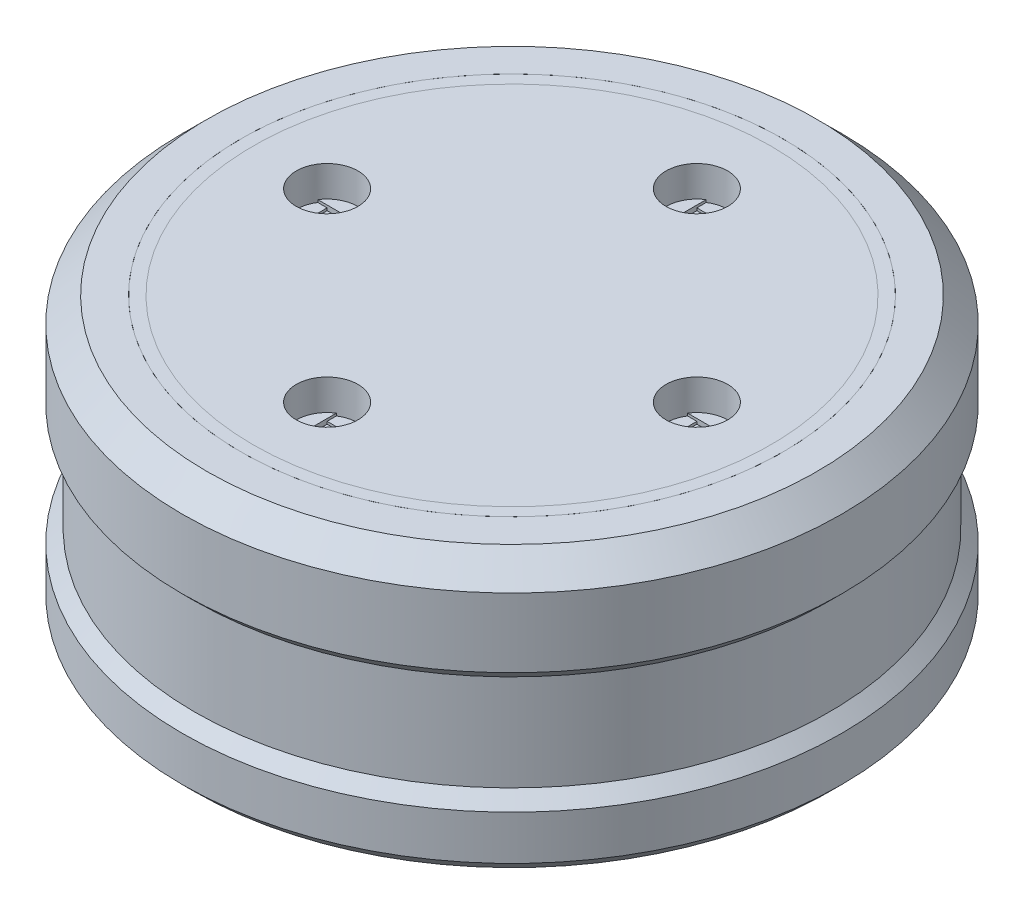
SolidWorks part; units mm, degrees
ref_plane "Front Plane" through (0, 0, 0) normal (0, 0, 1) x (1, 0, 0)
ref_plane "Top Plane" through (0, 0, 0) normal (0, 1, 0) x (1, 0, 0)
ref_plane "Right Plane" through (0, 0, 0) normal (1, 0, 0) x (0, 0, -1)
sketch "Sketch1" plane through (0, 0, 0) normal (0, 1, 0) x (1, 0, 0)
  circle A0 centre (0, 0) radius 15 construction
  circle A1 centre (0, 0) radius 26.75
  circle A2 centre (0, 15) radius 1.35
  circle A3 centre (15, 0) radius 1.35
  circle A4 centre (0, -15) radius 1.35
  circle A5 centre (-15, 0) radius 1.35
  dimension "D1" = 30
  dimension "D2" = 53.5
  dimension "D3" = 2.7
extrude "Boss-Extrude1" add sketch "Sketch1" along normal blind 25
sketch "Sketch2" plane through (0, 0, 0) normal (0, -1, 0) x (1, 0, 0)
  circle A0 centre (0, 0) radius 25
  dimension "D1" = 50
extrude "Cut-Extrude1" cut sketch "Sketch2" against normal offset from surface (20 mm away) 5 up to face at (0, 25, 16.35)
sketch "Sketch3" plane through (0, 0, 0) normal (1, 0, 0) x (0, 0, -1)
  line L0 (-26.75, 25) -> (-26.75, 0) construction
  line L1 (-26.75, 17.4) -> (-25.75, 17.4)
  line L2 (-26.75, 17.4) -> (-26.75, 7.6)
  line L3 (-26.75, 7.6) -> (-25.75, 7.6)
  line L4 (-25.75, 17.4) -> (-25.75, 7.6)
  line L5 (0, 0) -> (0, 25) construction
  line L6 (-26.75, 0) -> (26.75, 0) construction
  line L7 (1.35, 25) -> (-1.35, 25) construction
  point P12 (-25.75, 12.5)
  point P13 (0, 12.5)
  dimension "D1" = 9.8
  dimension "D2" = 1
revolve "Cut-Revolve1" cut sketch "Sketch3" angle 360 about L5
chamfer "Chamfer1" distance 2 angle 45 1 edges at (0, 25, 26.75)
chamfer "Chamfer2" distance 1 angle 45 2 edges at (0, 7.6, -25.75) (0, 17.4, -25.75)
chamfer "Chamfer3" distance 1 angle 45 1 edges at (0, 0, 26.75)
sketch "Sketch4" plane through (0, 25, 0) normal (0, 1, 0) x (1, 0, 0)
  circle A0 centre (0, 15) radius 2.5
  circle A1 centre (15, 0) radius 2.5
  circle A2 centre (0, -15) radius 2.5
  circle A3 centre (-15, 0) radius 2.5
  dimension "D1" = 5
extrude "Cut-Extrude2" cut sketch "Sketch4" against normal blind 2.5
sketch "Sketch5" plane through (0, 22.5, 0) normal (0, 1, 0) x (1, 0, 0)
  line L2 (-1.35, 12.8958) -> (-1.35, 17.1042)
  line L4 (1.35, 12.8958) -> (1.35, 17.1042)
  line L5 (-1.35, 12.8958) -> (1.35, 17.1042) construction
  line L6 (-1.35, 17.1042) -> (1.35, 12.8958) construction
  circle A0 centre (0, 15) radius 2.5 construction
  circle A1 centre (0, 15) radius 1.35 construction
  circle A2 centre (0, 15) radius 2.5 construction
  arc A3 (1.35, 17.1042) -> (-1.35, 17.1042) centre (0, 15) ccw
  arc A4 (-1.35, 12.8958) -> (1.35, 12.8958) centre (0, 15) ccw
  point P0 (0, 15)
extrude "Cut-Extrude3" cut sketch "Sketch5" against normal blind 0.2
sketch "Sketch6" plane through (0, 22.3, 0) normal (0, 1, 0) x (1, 0, 0)
  line L0 (1.35, 15) -> (1.35, 17.1042) construction
  line L1 (-1.35, 13.65) -> (1.35, 13.65)
  line L2 (-1.35, 13.65) -> (-1.35, 16.35)
  line L3 (-1.35, 16.35) -> (1.35, 16.35)
  line L4 (1.35, 13.65) -> (1.35, 16.35)
  line L5 (-1.35, 13.65) -> (1.35, 16.35) construction
  line L6 (-1.35, 16.35) -> (1.35, 13.65) construction
  arc A0 (1.35, 15) -> (-1.35, 15) centre (0, 15) ccw construction
  point P0 (0, 15)
extrude "Cut-Extrude4" cut sketch "Sketch6" against normal blind 0.2
pattern_circular "CirPattern1" count 4 every 90 about axis through (0, 25, 0) along (0, 1, 0) of "Cut-Extrude3", "Cut-Extrude4"
sketch "Sketch7" plane through (0, 0, 0) normal (0, 0, 1) x (1, 0, 0)
  line L0 (-26.75, 7.6) -> (-26.75, 1) construction
  line L1 (-26.75, 3) -> (26.75, 3)
  line L2 (-26.75, 3) -> (-26.75, 0)
  line L3 (-26.75, 0) -> (26.75, 0)
  line L4 (26.75, 3) -> (26.75, 0)
  line L5 (26.75, 1) -> (26.75, 7.6) construction
  line L6 (-25.75, 0) -> (25.75, 0) construction
  dimension "D1" = 3
extrude "Cut-Extrude5" cut sketch "Sketch7" against normal through all both and the other way through all
chamfer "Chamfer4" distance 1 angle 45 1 edges at (0, 3, 26.75)
sketch "Sketch8" plane through (0, 25, 0) normal (0, 1, 0) x (1, 0, 0)
  circle A0 centre (0, 0) radius 21
  circle A1 centre (0, 0) radius 22
  dimension "D1" = 44
  dimension "D2" = 42
extrude "Cut-Extrude6" cut sketch "Sketch8" against normal blind 0.6 and the other way through all
extrude "Boss-Extrude2" add sketch "Sketch8<2>" against normal up to surface (0.6 mm away) separate body up to face at (0, 24.4, 21)
sketch "Sketch8<2>" plane through (0, 25, 0) normal (0, 1, 0) x (1, 0, 0) same geometry as "Sketch8"
